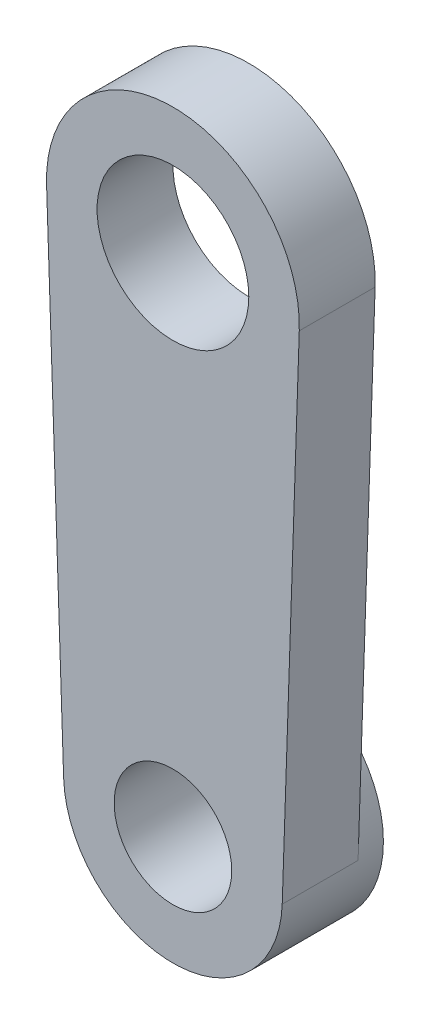
SolidWorks part; units mm, degrees
note: The reader was unsure of these and kept them because the rebuilt part matched: shared geometry of "Sketch1<3>".
ref_plane "Front Plane" through (0, 0, 0) normal (0, 0, 1) x (1, 0, 0)
ref_plane "Top Plane" through (0, 0, 0) normal (0, 1, 0) x (1, 0, 0)
ref_plane "Right Plane" through (0, 0, 0) normal (1, 0, 0) x (0, 0, -1)
sketch "Sketch1" plane through (0, 0, 0) normal (0, 0, 1) x (1, 0, 0)
  line L0 (0, 25) -> (0, -4.325)
  line L1 (4.9972, 19.8313) -> (4.3225, -0.146)
  line L2 (-4.9972, 19.8313) -> (-4.3225, -0.146)
  circle A6 centre (0, 0) radius 2.325
  circle A7 centre (0, 0) radius 4.325
  circle A8 centre (0, 20) radius 3
  circle A9 centre (0, 20) radius 5
  dimension "D1" = 4.65
  dimension "D2" = 2
  dimension "D3" = 6
  dimension "D5" = 2
  dimension "D4" = 20
extrude "Boss-Extrude1" add sketch "Sketch1" along normal blind 3
extrude "Boss-Extrude2" add sketch "Sketch1<3>" against normal blind 1
sketch "Sketch1<3>" plane through (0, 0, 0) normal (0, 0, 1) x (1, 0, 0) same geometry as "Sketch1"
